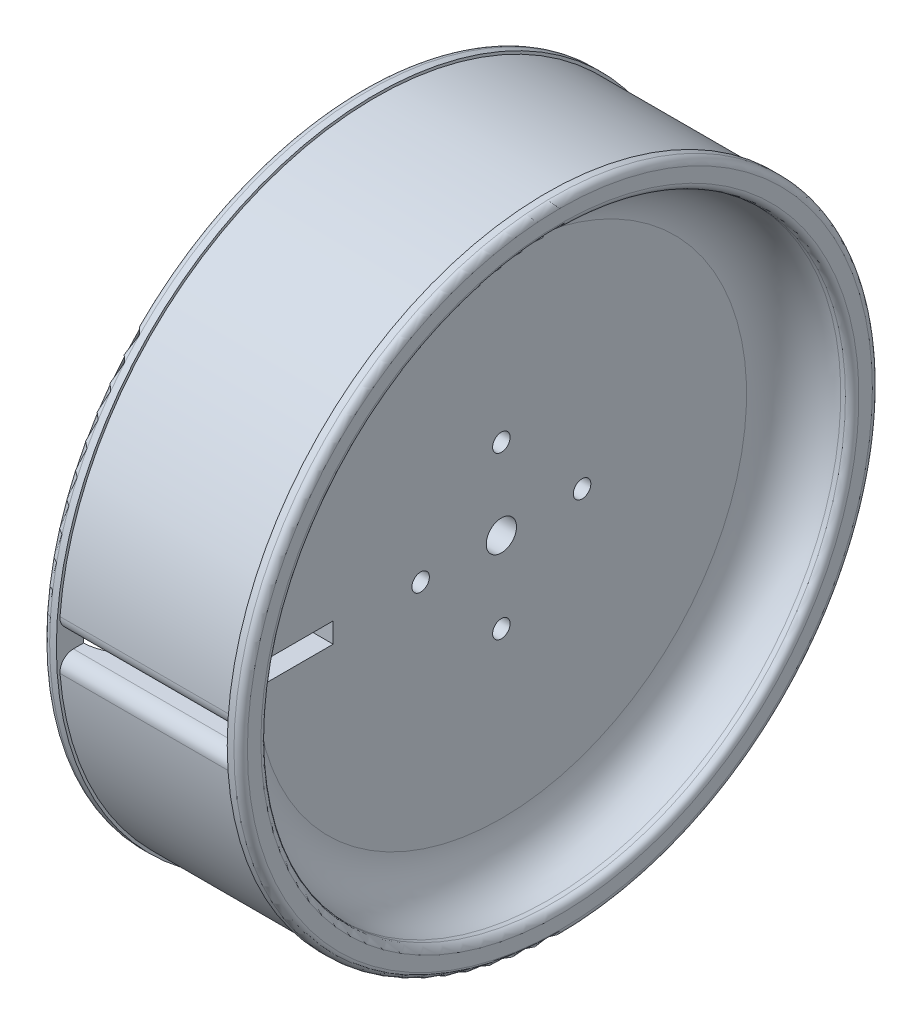
SolidWorks part; units mm, degrees
ref_plane "Front Plane" through (0, 0, 0) normal (0, 0, 1) x (1, 0, 0)
ref_plane "Top Plane" through (0, 0, 0) normal (0, 1, 0) x (1, 0, 0)
ref_plane "Right Plane" through (0, 0, 0) normal (1, 0, 0) x (0, 0, -1)
sketch "Sketch2" plane through (0, 0, 0) normal (0, 1, 0) x (1, 0, 0)
  line L0 (0, 0) -> (0, 45.9946) construction
  line L1 (-6, 0) -> (6, 0)
  line L3 (-14.7, 47.45) -> (-12.7, 47.45)
  line L4 (-12.7, 47.45) -> (-12.7, 47.05)
  line L5 (-12.7, 47.05) -> (12.7, 47.05)
  line L6 (12.7, 47.45) -> (12.7, 47.05)
  line L7 (14.7, 47.45) -> (12.7, 47.45)
  line L9 (-14.7, 47.45) -> (-14.7, 43.45)
  line L10 (-14.7, 43.45) -> (-6, 43.45)
  line L11 (-6, 43.45) -> (-6, 0)
  line L12 (6, 0) -> (6, 43.45)
  line L13 (6, 43.45) -> (14.7, 43.45)
  line L14 (14.7, 43.45) -> (14.7, 47.45)
  point P5 (0, 0)
  point P11 (0, 47.05)
  dimension "D1" = 25.4
  dimension "D2" = 0.4
  dimension "D3" = 2
  dimension "D4" = 4
  dimension "D5" = 12
  dimension "D6" = 47.05
revolve "Revolve1" add sketch "Sketch2" angle 360 about L1
sketch "Sketch3" plane through (6, 0, 0) normal (1, 0, 0) x (0, 0, -1)
  circle A0 centre (0, 0) radius 2.25
  circle A1 centre (0, 0) radius 12 construction
  circle A2 centre (0, 12) radius 1.3
  circle A3 centre (-12, 0) radius 1.3
  circle A4 centre (0, -12) radius 1.3
  circle A5 centre (12, 0) radius 1.3
  dimension "D1" = 4.5
  dimension "D2" = 24
  dimension "D3" = 2.6
extrude "Cut-Extrude1" cut sketch "Sketch3" against normal up to next
sketch "Sketch6" plane through (0, 0, 0) normal (0, 0, 1) x (1, 0, 0)
  line L0 (12.7, 47.05) -> (12.7, -47.05) construction
  line L1 (-12.7, -1.5) -> (12.7, -1.5)
  line L2 (-12.7, -1.5) -> (-12.7, 1.5)
  line L3 (-12.7, 1.5) -> (12.7, 1.5)
  line L4 (12.7, -1.5) -> (12.7, 1.5)
  line L5 (-12.7, -1.5) -> (12.7, 1.5) construction
  line L6 (-12.7, 1.5) -> (12.7, -1.5) construction
  point P0 (0, 0)
  dimension "D1" = 3
extrude "Cut-Extrude2" cut sketch "Sketch6" along normal through all from offset 25
fillet "Fillet1" radius 1 4 edges at (-14.7, 0, 47.45) (-14.7, 0, 43.45) (14.7, 0, 43.45) (14.7, 0, 47.45)
fillet "Fillet2" radius 7 2 edges at (-6, 0, -43.45) (6, 0, -43.45)
fillet "Fillet3" radius 2 2 edges at (0, -1.5, 47.0261) (0, 1.5, 47.0261)
